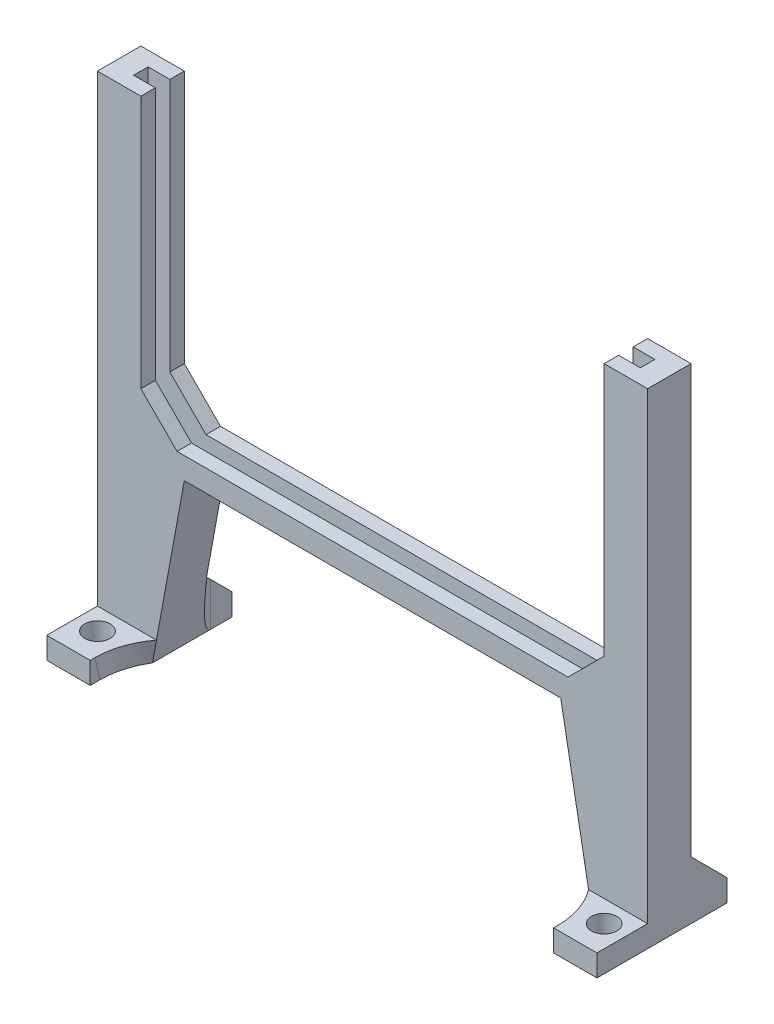
SolidWorks part; units mm, degrees
ref_plane "Front Plane" through (0, 0, 0) normal (0, 0, 1) x (1, 0, 0)
ref_plane "Top Plane" through (0, 0, 0) normal (0, 1, 0) x (1, 0, 0)
ref_plane "Right Plane" through (0, 0, 0) normal (1, 0, 0) x (0, 0, -1)
sketch "Sketch1" plane through (0, 0, 0) normal (0, 1, 0) x (1, 0, 0)
  line L1 (-3, 9) -> (3, 9)
  line L2 (-3, 9) -> (-3, -4)
  line L3 (-3, -4) -> (3, -4)
  line L4 (3, 9) -> (3, -4)
  line L5 (67, 9) -> (73, 9)
  line L6 (67, 9) -> (67, -4)
  line L7 (67, -4) -> (73, -4)
  line L8 (73, 9) -> (73, -4)
  circle A0 centre (0, 0) radius 1.75
  circle A1 centre (70, 0) radius 1.75
  point P13 (0, 9)
  point P14 (70, 9)
  dimension "D1" = 3.5
  dimension "D2" = 70
  dimension "D3" = 6
  dimension "D4" = 4
  dimension "D5" = 13
extrude "Boss-Extrude1" add sketch "Sketch1" along normal blind 3 contours L4 L1 L2 L3 A0 | L8 L5 L6 L7 A1 region at (0, 0, -2.8518) region at (70, 0, -2.8518)
ref_plane "Plane1" through (0, 0, -5) normal (0, 0, -1) x (-1, 0, 0)
sketch "Sketch3" plane through (0, 0, -5) normal (0, 0, -1) x (-1, 0, 0)
  line L0 (-73, 0) -> (-65.396, 0)
  line L1 (-67, 0) -> (-73, 0) construction
  line L2 (-65.396, 0) -> (-61, 24)
  line L3 (-61, 24) -> (-9, 24)
  line L4 (-9, 24) -> (-4.604, 0)
  line L5 (-4.604, 0) -> (3, 0)
  line L6 (-73, 0) -> (-73, 27)
  line L7 (-73, 27) -> (3, 27)
  line L8 (3, 27) -> (3, 0)
  dimension "D1" = 24
  dimension "D2" = 52
  dimension "D3" = 3
extrude "Boss-Extrude2" add sketch "Sketch3" against normal blind 2 and the other way up to surface (4 mm away) other way up to face at (0, 1.5, -9)
sketch "Sketch4" plane through (0, 27, 0) normal (0, 1, 0) x (1, 0, 0)
  line L0 (3, 9) -> (-3, 9)
  line L1 (-3, 9) -> (73, 9) construction
  line L2 (-3, 9) -> (-3, 3)
  line L3 (-3, 3) -> (3, 3)
  line L4 (-3, 3) -> (73, 3) construction
  line L5 (3, 3) -> (3, 5)
  line L6 (3, 5) -> (0, 5)
  line L7 (0, 5) -> (0, 7)
  line L8 (0, 7) -> (3, 7)
  line L9 (3, 7) -> (3, 9)
  line L10 (67, 3) -> (73, 3)
  line L11 (73, 3) -> (73, 9)
  line L12 (73, 9) -> (73, 3) construction
  line L13 (73, 9) -> (67, 9)
  line L14 (67, 9) -> (67, 7)
  line L15 (67, 7) -> (70, 7)
  line L16 (70, 7) -> (70, 5)
  line L17 (70, 5) -> (67, 5)
  line L18 (67, 5) -> (67, 3)
  dimension "D1" = 2
  dimension "D2" = 70
  dimension "D3" = 3
extrude "Boss-Extrude3" add sketch "Sketch4" along normal blind 40
sketch "Sketch5" plane through (0, 27, 0) normal (0, 1, 0) x (1, 0, 0)
  line L1 (0, 7) -> (70, 7)
  line L2 (0, 7) -> (0, 5)
  line L3 (0, 5) -> (70, 5)
  line L4 (70, 7) -> (70, 5)
extrude "Cut-Extrude1" cut sketch "Sketch5" against normal blind 2
chamfer "Chamfer1" distance 5 angle 45 4 edges at (67, 27, -4) (67, 27, -8) (3, 27, -8) (3, 27, -4)
fillet "Fillet1" radius 10 2 edges at (67, 1.5, -3) (3, 1.5, -3)
sketch "Sketch6" plane through (0, 0, -9) normal (0, 0, -1) x (-1, 0, 0)
  line L0 (-73, 3) -> (-64.8465, 3) construction
  line L1 (-73, 0) -> (-65.396, 0)
  line L2 (-73, 0) -> (-73, 3)
  line L3 (-73, 3) -> (-65.396, 3)
  line L4 (-65.396, 0) -> (-65.396, 3)
  line L6 (-4.604, 0) -> (3, 0)
  line L7 (-4.604, 0) -> (-4.604, 3)
  line L8 (-4.604, 3) -> (3, 3)
  line L9 (3, 0) -> (3, 3)
  line M9 (-4.604, 0) -> (3, 0)
  line M10 (3, 0) -> (3, 67)
extrude "Boss-Extrude4" add sketch "Sketch6" along normal blind 5 contours L8 L7 M9 M10 | L3 L4 L1 L2 region at (0.802, 1.5, -9)
fillet "Fillet2" radius 2 2 edges at (4.604, 1.5, -9) (65.396, 1.5, -9)
chamfer "Chamfer2" distance 5 angle 45 2 edges at (1.0768, 3, -9) (68.9232, 3, -9)
